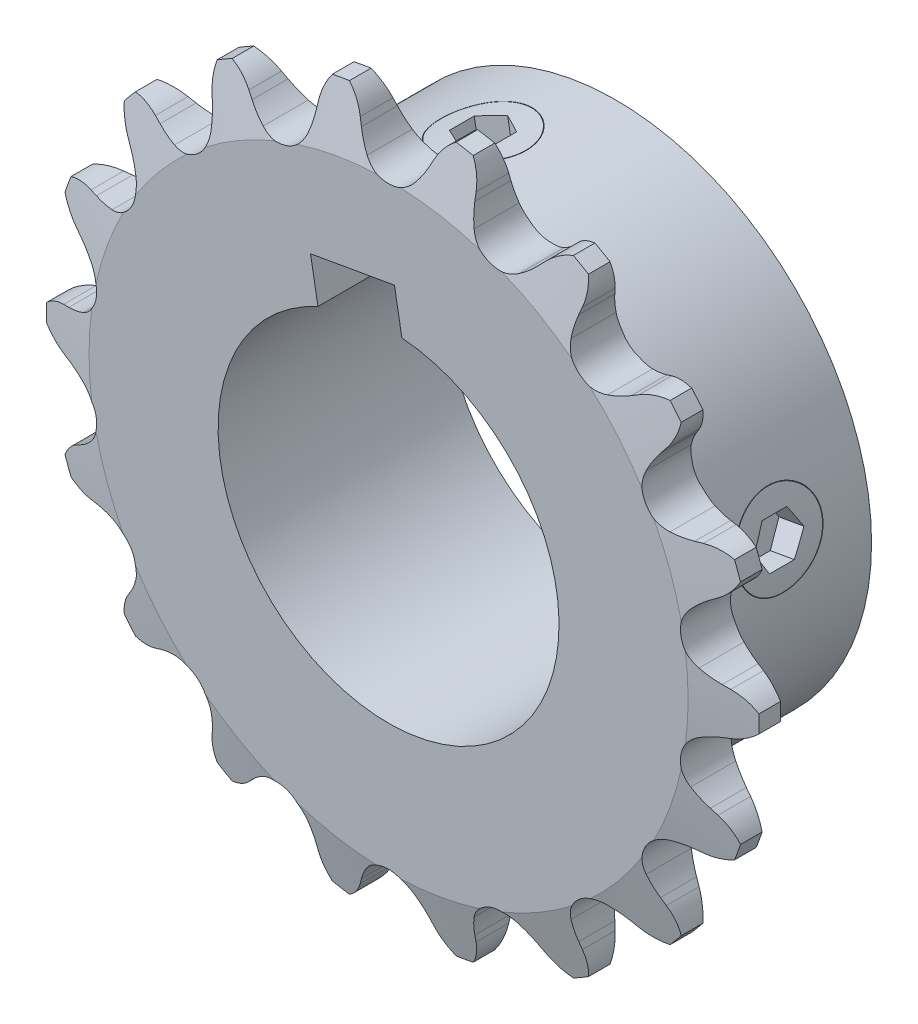
SolidWorks part; units mm, degrees
ref_plane "Front Plane" through (0, 0, 0) normal (0, 0, 1) x (1, 0, 0)
ref_plane "Top Plane" through (0, 0, 0) normal (0, 1, 0) x (1, 0, 0)
ref_plane "Right Plane" through (0, 0, 0) normal (1, 0, 0) x (0, 0, -1)
ref_axis "Axis1" through (0, 0, -88.99) along (0, 0, 1)
sketch "Sprocket-BaseSketch" plane through (0, 0, 0) normal (1, 0, 0) x (0, 0, -1)
  line L0 (1.397, 0) -> (1.397, 16.7363)
  line L1 (1.397, 16.7363) -> (0.6032, 19.9113)
  line L2 (0.6032, 19.9113) -> (-0.6032, 19.9113)
  line L3 (-0.6032, 19.9113) -> (-1.397, 16.7363)
  line L4 (-1.397, 16.7363) -> (-1.397, 0)
  line L5 (-1.397, 0) -> (1.397, 0)
  line L6 (5.588, 0) -> (-1.7463, 0) construction
  dimension "Hub Surface" = 1.397
  dimension "RightSide (1)" = 0.7938
  dimension "RightSide (2)" = 3.175
  dimension "OD" = 19.9113
  dimension "LeftSide (1)" = 0.7938
  dimension "LeftSide (2)" = 3.175
  dimension "Tooth Width" = 2.794
revolve "25 (04C) ANSI (ISO) Chain Number, 1.440in P.D." add sketch "Sprocket-BaseSketch" angle 360 about L6
sketch "Tooth-Sketch" plane through (0, 0, 0) normal (0, 0, 1) x (1, 0, 0)
  line L0 (0, 0) -> (0, 24.3788) construction
  line L1 (1.9086, 18.1962) -> (2.0662, 18.5596)
  line L2 (-1.9086, 18.1962) -> (-2.0662, 18.5596)
  line L3 (0, 18.2841) -> (6.2535, 17.1814) construction
  line L4 (0, 18.2841) -> (-6.2535, 17.1814) construction
  arc A0 (-1.3314, 17.2313) -> (1.3314, 17.2313) centre (0, 18.2841) ccw
  arc A1 (1.3314, 17.2313) -> (1.9086, 18.1962) centre (-2.0721, 19.9225) ccw
  arc A2 (-1.3314, 17.2313) -> (-1.9086, 18.1962) centre (2.0721, 19.9225) cw
  arc A3 (2.0662, 18.5596) -> (4.5526, 20.1914) centre (4.5526, 17.4814) cw
  arc A4 (-2.0662, 18.5596) -> (-4.5526, 20.1914) centre (-4.5526, 17.4814) ccw
  arc A5 (4.5526, 20.1914) -> (-4.5526, 20.1914) centre (0, 0) ccw
extrude "Tooth-Cut, Number of teeth: 18" cut sketch "Tooth-Sketch" against normal through all and the other way through all
pattern_circular "Tooth Pattern, 18 / 18" count 18 every 20 about axis through (0, 0, -88.99) along (0, 0, 1) of "Tooth-Cut, Number of teeth: 18"
sketch "Sketch3" plane through (0, 0, 0) normal (1, 0, 0) x (0, 0, -1)
  line L0 (-9.906, 0) -> (9.906, 0) construction
  line L1 (1.397, 0) -> (1.397, 14.2875)
  line L2 (1.397, 14.2875) -> (11.303, 14.2875)
  line L3 (11.303, 14.2875) -> (11.303, 0)
  line L4 (11.303, 0) -> (1.397, 0)
  dimension "Hub Mounting" = 1.397
  dimension "Hub OD" = 14.2875
  dimension "Hub Width" = 9.906
revolve "Hub-Revolve1" add sketch "Sketch3" angle 360 about L0
sketch "Sketch4" plane through (0, 0, -11.303) normal (0, 0, -1) x (-1, 0, 0)
  circle A0 centre (0, 0) radius 9.525
  dimension "Bore Diameter " = 19.05
extrude "Cut-Extrude1" cut sketch "Sketch4" against normal through all
sketch "Sketch5" plane through (0, 0, 0) normal (1, 0, 0) x (0, 0, -1)
  line L0 (11.303, 0) -> (-1.397, 0) construction
  line L1 (11.303, -14.2875) -> (11.303, 14.2875) construction
  line L2 (-1.397, 2.2476) -> (-1.397, -2.2476) construction
ref_plane "Plane1" through (0, 0, 0) normal (-0.1736, 0.9848, 0) x (-0.9848, -0.1736, 0)
sketch "Sketch6" plane through (0, 0, -11.303) normal (0, 0, -1) x (-1, 0, 0)
  line L0 (-0.7436, 9.4959) -> (-0.3301, 11.841)
  line L1 (-0.3301, 11.841) -> (4.3601, 11.014)
  line L2 (4.3601, 11.014) -> (3.9466, 8.6689)
  line L3 (3.9466, 8.6689) -> (-0.7436, 9.4959)
  line L4 (6.8789, -1.2129) -> (-6.8789, 1.2129) construction
  circle A0 centre (0, 0) radius 9.525 construction
  dimension "Keyway Wd " = 4.7625
  dimension "Keyway Dp " = 2.3813
extrude "Cut-Extrude2" cut sketch "Sketch6" against normal through all
sketch "Sketch7" plane through (-2.015, 11.4275, 0) normal (0.1736, -0.9848, 0) x (0.9848, 0.1736, 0)
  line L0 (0, -11.303) -> (0, -1.397) construction
  line L1 (-2.3813, -11.303) -> (2.3812, -11.303) construction
  line L2 (-2.2476, -1.397) -> (2.2476, -1.397) construction
  line L3 (-2.3813, 1.397) -> (-2.3813, -11.303) construction
  circle A0 centre (0, -6.35) radius 2.3813
extrude "Cut-Extrude3" cut sketch "Sketch7" against normal through all draft 1 draft outward yes
sketch "Sketch8" plane through (-2.015, 11.4275, 0) normal (0.1736, -0.9848, 0) x (0.9848, 0.1736, 0)
  line L0 (0, -6.35) -> (-2.3813, -6.35) construction
  line L1 (-2.3813, 1.397) -> (-2.3813, -11.303) construction
  line L2 (-2.3813, -6.35) -> (-2.4245, -6.35) construction
  line L3 (-2.4029, -6.35) -> (-2.4029, -11.303) construction
  line L4 (-14.2875, -11.303) -> (14.2875, -11.303) construction
  circle A0 centre (0, -6.35) radius 2.4029
  arc A1 (-2.3813, -6.35) -> (2.3813, -6.35) centre (0, -6.35) ccw construction
  spline S0 degree 3 poles (-2.408, -6.6748) (-2.3444, -6.9895) (-2.2977, -7.1409) (-2.1759, -7.4326) (-2.0997, -7.5743) (-1.9225, -7.8379) (-1.8221, -7.9596) (-1.5978, -8.1831) (-1.473, -8.2851) (-1.2098, -8.4602) (-1.0704, -8.5345) (-0.7754, -8.6561) (-0.622, -8.7022) (-0.3115, -8.7632) (-0.1522, -8.7786) (0.1677, -8.7776) (0.3253, -8.7614) (0.636, -8.6984) (0.7905, -8.6509) (1.083, -8.5282) (1.222, -8.4532) (1.4855, -8.2755) (1.6092, -8.173) (1.8314, -7.9489) (1.9316, -7.8262) (2.1083, -7.5595) (2.1822, -7.4197) (2.3023, -7.1273) (2.3487, -6.9729) (2.4098, -6.6605) (2.4249, -6.5029) (2.4241, -6.1852) (2.4078, -6.0242) (2.3137, -5.5582) (2.1882, -5.2578) (1.9243, -4.8646) (1.8227, -4.741) (1.5973, -4.5164) (1.4751, -4.4165) (1.2119, -4.2411) (1.0694, -4.1651) (0.7764, -4.0443) (0.6251, -3.9986) (0.3125, -3.9369) (0.152, -3.9215) (-0.1646, -3.9223) (-0.3229, -3.9382) (-0.6372, -4.0018) (-0.7886, -4.0485) (-1.0805, -4.1706) (-1.2223, -4.2471) (-1.4854, -4.4244) (-1.607, -4.525) (-1.8304, -4.7499) (-1.9321, -4.8747) (-2.1941, -5.2696) (-2.3179, -5.5708) (-2.4094, -6.0365) (-2.4249, -6.1962) (-2.4241, -6.5162) (-2.408, -6.6748) (-2.3444, -6.9895) (-2.2977, -7.1409) knots -0.03125 -0.03125 0 0 0.03125 0.03125 0.0625 0.0625 0.09375 0.09375 0.125 0.125 0.15625 0.15625 0.1875 0.1875 0.21875 0.21875 0.25 0.25 0.28125 0.28125 0.3125 0.3125 0.34375 0.34375 0.375 0.375 0.40625 0.40625 0.4375 0.4375 0.46875 0.46875 0.5 0.5 0.5625 0.5625 0.59375 0.59375 0.625 0.625 0.65625 0.65625 0.6875 0.6875 0.71875 0.71875 0.75 0.75 0.78125 0.78125 0.8125 0.8125 0.84375 0.84375 0.875 0.875 0.9375 0.9375 0.96875 0.96875 1 1 1.03125 1.03125 1.0625 only from (-2.3762, -6.8321) to (-2.3762, -6.8321) construction
extrude "Extrude1" add sketch "Sketch8" against normal up to surface (2.4802 mm away) up to face at (-0.2684, 14.285, -5.3655)
sketch "Sketch9" plane through (-2.015, 11.4275, 0) normal (0.1736, -0.9848, 0) x (0.9848, 0.1736, 0)
  line L0 (0, -6.35) -> (2.4029, -6.35) construction
  line L1 (1.2014, -6.35) -> (1.2014, -8.4309) construction
  line L3 (0, -7.7373) -> (1.2014, -7.0436)
  line L4 (1.2014, -7.0436) -> (1.2014, -5.6564)
  line L5 (1.2014, -5.6564) -> (0, -4.9627)
  line L6 (0, -4.9627) -> (-1.2014, -5.6564)
  line L7 (-1.2014, -5.6564) -> (-1.2014, -7.0436)
  line L8 (-1.2014, -7.0436) -> (0, -7.7373)
  circle A0 centre (0, -6.35) radius 2.4029 construction
  circle A1 centre (0, -6.35) radius 1.2014 construction
extrude "Cut-Extrude4" cut sketch "Sketch9" against normal through all from offset 1.27 offset against normal yes
pattern_circular "CirPattern1" count 2 over 90 about axis through (0, 0, 9.906) along (0, 0, -1) of "Cut-Extrude3", "Extrude1", "Cut-Extrude4"
sketch "Sketch10" plane through (0, 0, -11.303) normal (0, 0, -1) x (-1, 0, 0)
  line L0 (-19.6088, 3.4576) -> (19.6088, -3.4576)
  line L1 (-6.2535, -17.1814) -> (0, -18.2841)
  line L2 (6.8789, -1.2129) -> (-6.8789, 1.2129) construction
  line L3 (-19.879, 1.9254) -> (19.3387, -4.9897)
  line L4 (-5.9834, -15.6493) -> (0.2702, -16.752)
  circle A0 centre (0, 0) radius 19.9113
  circle A1 centre (0, 0) radius 9.525
  arc A2 (-0.7436, 9.4959) -> (3.9466, 8.6689) centre (0, 0) ccw construction
  arc A3 (15.5605, 12.423) -> (14.9363, 13.1669) centre (0, 0) ccw construction
  dimension "D1" = 1.5557
  dimension "D2" = 1.5557
equation "\"D1@Sketch10\" = \"D2@Sketch10\""
